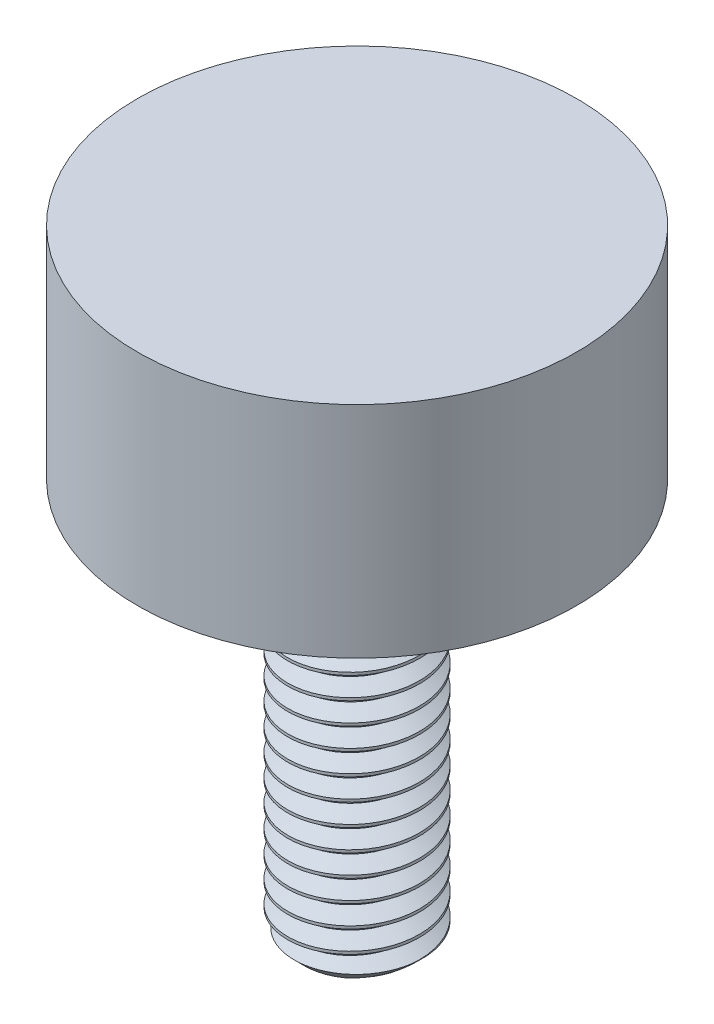
SolidWorks part; units mm, degrees
ref_plane "Front Plane" through (0, 0, 0) normal (0, 0, 1) x (1, 0, 0)
ref_plane "Top Plane" through (0, 0, 0) normal (0, 1, 0) x (1, 0, 0)
ref_plane "Right Plane" through (0, 0, 0) normal (1, 0, 0) x (0, 0, -1)
sketch "Sketch1" plane through (0, 0, 0) normal (0, 0, 1) x (1, 0, 0)
  line L0 (0, 14) -> (0, -14) construction
  line L1 (10, 0) -> (-10, 0) construction
  line L2 (3, -14) -> (-3, -14) construction
  line L3 (-3, -14) -> (-3, -13) construction
  point P3 (0, 4)
  point P4 (3, -11.5)
  point P8 (0, 0)
  point P10 (0, -14)
  dimension "Thread Length" = 18
  dimension "Height" = 10
  dimension "OD" = 20
  dimension "Thread Size" = 6
  dimension "Thread Pitch" = 1
  dimension "D1" = 2.5
sketch "Sketch2" plane through (0, 0, 0) normal (0, 0, 1) x (1, 0, 0)
  line L0 (-10, 4) -> (-8, 4)
  line L1 (-10, 14) -> (0, 14)
  line L2 (0, 14) -> (0, -14) construction
  line L3 (-10, 4) -> (-10, 14)
  line L4 (0, 14) -> (0, 4) construction
  line L5 (0, 14) -> (0, 9.1)
  line L6 (0, 9.1) -> (-3.15, 9.1)
  line L7 (-3.15, 9.1) -> (-3.15, 4.2)
  line L8 (0, 4) -> (0, -14) construction
  line L9 (3, 4) -> (3, 9.1) construction
  line L10 (-8, 4) -> (-8, 4.2)
  line L11 (-8, 4.2) -> (-3.15, 4.2)
  dimension "D2" = 16
  dimension "D3" = 0.2
  dimension "D1" = 6.3
revolve "Revolve1" add sketch "Sketch2" angle 360 about L4
sketch "Sketch3" plane through (0, 0, 0) normal (0, 0, 1) x (1, 0, 0)
  line L0 (-8, 4.2) -> (-3.15, 4.2)
  line L1 (-8, 4.2) -> (-3.15, 4.2) construction
  line L2 (-3.15, 4.2) -> (-3.15, 4.1)
  line L5 (-3.15, 4) -> (-3.25, 4)
  line L6 (-8, 4) -> (-8, 4.2)
  line L7 (-3.15, 9.1) -> (-3.15, 4.2) construction
  line L8 (-3.25, 4) -> (-8, 4)
  line L9 (-3.15, 4.1) -> (-3.15, 4)
revolve "Revolve2" add sketch "Sketch3" angle 360 about L0
sketch "Sketch5" plane through (0, 0, 0) normal (0, 0, 1) x (1, 0, 0)
  line L0 (-2.4, -14) -> (0, -14)
  line L1 (-3.15, 9.1) -> (0, 9.1)
  line L2 (-3.15, 9.1) -> (-3.15, 4)
  line L3 (-3, -14) -> (-2.4, -14) construction
  line L4 (0, 9.1) -> (0, -14)
  line L5 (-3, -13.4) -> (-3, -14) construction
  line L6 (-3, -13.4) -> (-2.4, -14)
  line L7 (-3, 3.85) -> (-3, -13.4)
  line L8 (-3.15, 4) -> (-3, 3.85)
  dimension "D2" = 45
revolve "Revolve3" add sketch "Sketch5" angle 360 about L4
sketch "Sketch6" plane through (0, -14, 0) normal (0, -1, 0) x (1, 0, 0)
  circle A0 centre (0, 0) radius 3.15 construction
  circle A2 centre (0, 0) radius 3.15
curve "Helix/Spiral1" pitch 1 height 28 radius 3.15 centre (0, -14, 0) axis (0, 1, 0) start towards (1, 0, 0)
sketch "Sketch7" plane through (0, 0, 0) normal (0, 0, 1) x (1, 0, 0)
  line L0 (-3.1083, -13.9375) -> (-3.1083, -14.9375) construction
  line L1 (-3.1083, -14.9375) -> (-2.2422, -14.4375) construction
  line L2 (-2.2422, -14.4375) -> (-3.1083, -13.9375) construction
  line L3 (-2.3505, -14.375) -> (-2.3505, -14.5) construction
  line L4 (-3, -14) -> (-3, -14.875) construction
  line L5 (-3.1083, -14.4375) -> (-3, -14.4375) construction
  line L6 (-2.3505, -14.4375) -> (-2.2422, -14.4375) construction
  line L7 (-3.0541, -14.4375) -> (-3.0541, -14.9062) construction
  line L8 (-3.1083, -13.9375) -> (-3, -14.875)
  line L9 (-3, -14.875) -> (-2.3505, -14.5)
  line L10 (-2.3505, -14.5) -> (-2.3505, -14.375)
  line L11 (-2.3505, -14.375) -> (-3.1083, -13.9375)
  dimension "D2" = 0.125
sweep "Cut-Sweep1" cut profiles "Sketch7" path "Helix/Spiral1" align with end faces yes
sketch "Sketch8" plane through (0, 0, 0) normal (0, 0, 1) x (1, 0, 0)
  line L1 (-3.15, 9.1) -> (0, 9.1)
  line L2 (-3.15, 9.1) -> (-3.15, 4)
  line L3 (-3.15, 4) -> (0, 0.85)
  line L4 (0, 9.1) -> (0, 0.85)
  line L5 (-3.15, 4) -> (-3, 3.85) construction
revolve "Revolve4" add sketch "Sketch8" angle 360 about L4
equation "\"D2@Sketch2\"=\"OD@Sketch1\"*.8"
equation "\"D3@Sketch2\"=\"Height@Sketch1\"*.02"
equation "\"D3@Helix/Spiral1\"=\"Thread Length@Sketch1\"+\"Height@Sketch1\""
equation "\"D4@Helix/Spiral1\"=\"Thread Pitch@Sketch1\""
equation "\"D1@Sketch7\"=\"Thread Pitch@Sketch1\""
equation "\"D2@Sketch7\"=\"Thread Pitch@Sketch1\"/8"
equation "\"D1@Sketch5\"=\"Thread Size@Sketch1\"*.1"
equation "\"D1@Sketch2\"=\"Thread Size@Sketch1\"*1.05"
equation "\"D1@Sketch1\"=\"Thread Pitch@Sketch1\"*2.5"
